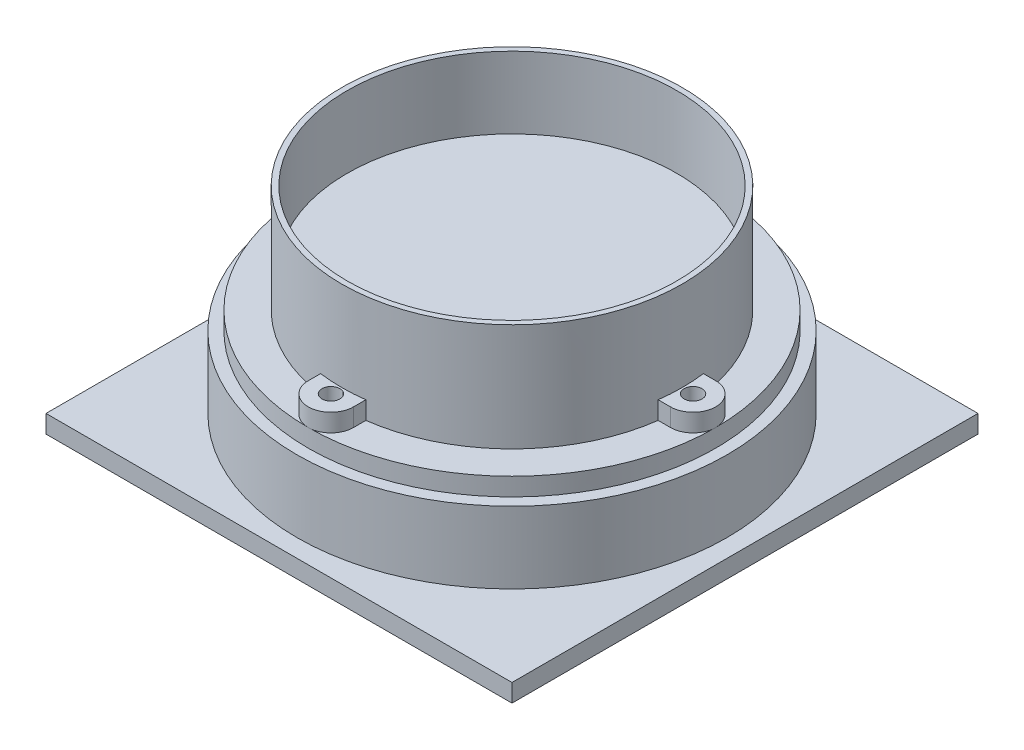
SolidWorks part; units mm, degrees
material "1060 Alloy"
ref_plane "Front Plane" through (0, 0, 0) normal (0, 0, 1) x (1, 0, 0)
ref_plane "Top Plane" through (0, 0, 0) normal (0, 1, 0) x (1, 0, 0)
ref_plane "Right Plane" through (0, 0, 0) normal (1, 0, 0) x (0, 0, -1)
sketch "Sketch1" plane through (0, 0, 0) normal (0, 1, 0) x (1, 0, 0)
  circle A0 centre (0, 0) radius 120.65
  dimension "D1" = 241.3
extrude "Boss-Extrude1" add sketch "Sketch1" along normal blind 63.5
sketch "Sketch2" plane through (0, 63.5, 0) normal (0, 1, 0) x (1, 0, 0)
  circle A0 centre (0, 0) radius 116.84
  dimension "D1" = 233.68
extrude "Cut-Extrude1" cut sketch "Sketch2" against normal blind 50.8
sketch "Sketch4" plane through (0, 0, 0) normal (0, -1, 0) x (1, 0, 0)
  line L0 (-16.0263, 119.5809) -> (-16.0263, 128.3248)
  line L1 (16.0263, 119.5809) -> (16.0263, 128.3248)
  line L2 (119.5809, -16.0263) -> (128.3248, -16.0263)
  line L3 (119.5809, 16.0263) -> (128.3248, 16.0263)
  line L4 (-16.0263, -119.5809) -> (-16.0263, -128.3248)
  line L5 (16.0263, -119.5809) -> (16.0263, -128.3248)
  line L6 (-119.5809, 16.0263) -> (-128.3248, 16.0263)
  line L7 (-119.5809, -16.0263) -> (-128.3248, -16.0263)
  circle A0 centre (0, 0) radius 120.65 construction
  arc A1 (-16.0263, 128.3248) -> (16.0263, 128.3248) centre (0, 128.3248) cw
  circle A2 centre (0, 0) radius 120.65
  arc A3 (128.3248, 16.0263) -> (128.3248, -16.0263) centre (128.3248, 0) cw
  arc A4 (16.0263, -128.3248) -> (-16.0263, -128.3248) centre (0, -128.3248) cw
  arc A5 (-128.3248, -16.0263) -> (-128.3248, 16.0263) centre (-128.3248, 0) cw
  point P27 (0, 0)
  circle M3 centre (0, 0) radius 120.65
  dimension "D1" = 4
extrude "Boss-Extrude3" add sketch "Sketch4" along normal blind 12.7 contours A5 L7 L6 M3 | A1 L0 L1 M3 | M3 | A3 L3 L2 M3 | A4 L5 L4 M3 region at (0, 0, 130.9109) region at (0, 0, 0) region at (-130.9109, 0, 0) region at (130.9109, 0, 0) region at (0, 0, -130.9109)
sketch "Sketch5" plane through (0, -12.7, 0) normal (0, -1, 0) x (1, 0, 0)
  circle A0 centre (0, 0) radius 144.3511
extrude "Boss-Extrude4" add sketch "Sketch5" along normal blind 12.7
sketch "Sketch6" plane through (0, -25.4, 0) normal (0, -1, 0) x (1, 0, 0)
  circle A0 centre (0, 0) radius 152.4
extrude "Boss-Extrude5" add sketch "Sketch6" along normal blind 50.8
sketch "Sketch7" plane through (0, 0, 0) normal (0, 1, 0) x (1, 0, 0)
  circle A0 centre (0, 128.3248) radius 6.35
  circle A1 centre (-128.3248, 0) radius 6.35
  circle A2 centre (0, -128.3248) radius 6.35
  circle A3 centre (128.3248, 0) radius 6.35
  circle A4 centre (0, 0) radius 128.3248 construction
  dimension "D1" = 12.7
  dimension "D2" = 12.7
  dimension "D3" = 12.7
  dimension "D4" = 12.7
  dimension "D5" = 256.6496
sketch "Sketch8" plane through (0, -76.2, 0) normal (0, -1, 0) x (1, 0, 0)
  line L1 (-165.1, -165.1) -> (165.1, -165.1)
  line L2 (-165.1, -165.1) -> (-165.1, 165.1)
  line L3 (-165.1, 165.1) -> (165.1, 165.1)
  line L4 (165.1, -165.1) -> (165.1, 165.1)
  line L5 (-165.1, -165.1) -> (165.1, 165.1) construction
  line L6 (-165.1, 165.1) -> (165.1, -165.1) construction
  point P0 (0, 0)
  dimension "D1" = 330.2
  dimension "D2" = 330.2
extrude "Boss-Extrude6" add sketch "Sketch8" along normal blind 12.7
extrude "Cut-Extrude2" cut sketch "Sketch7" against normal through all
